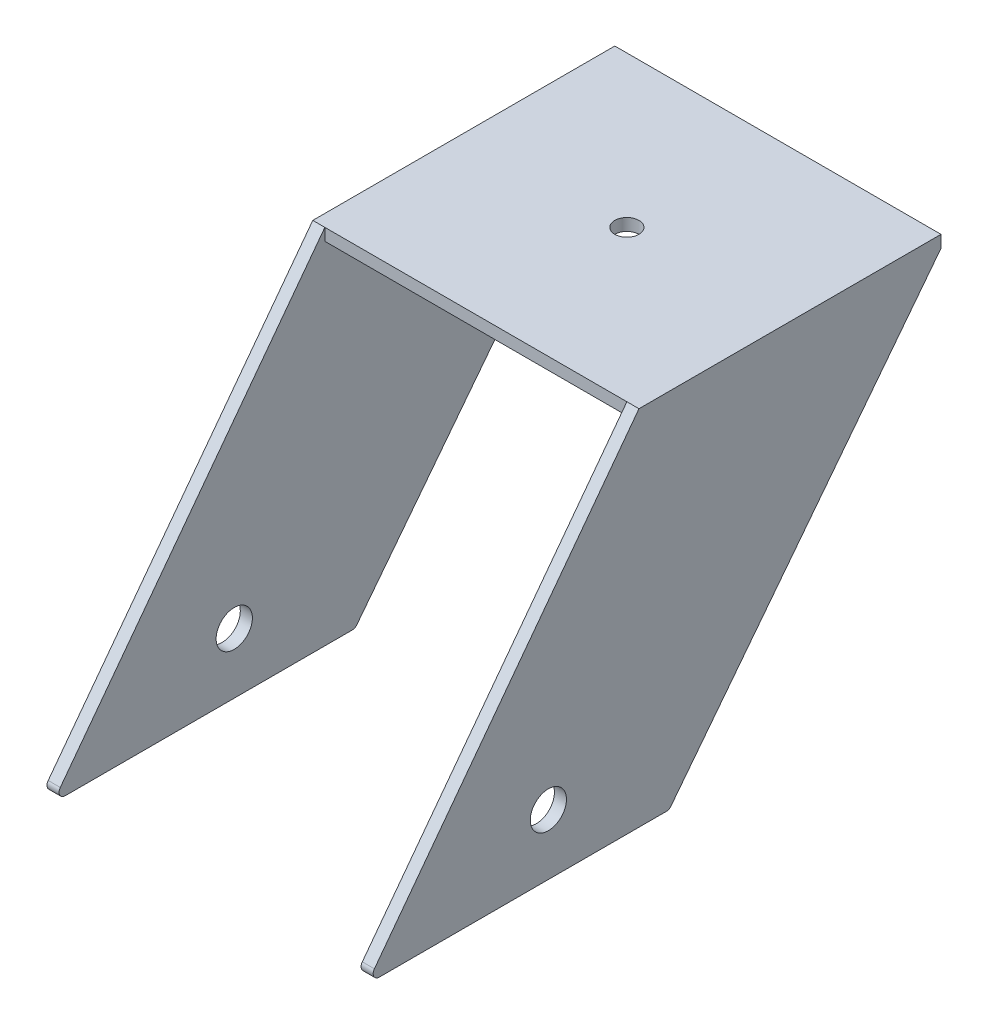
SolidWorks part; units mm, degrees
ref_plane "Front Plane" through (0, 0, 0) normal (0, 0, 1) x (1, 0, 0)
ref_plane "Top Plane" through (0, 0, 0) normal (0, 1, 0) x (1, 0, 0)
ref_plane "Right Plane" through (0, 0, 0) normal (1, 0, 0) x (0, 0, -1)
sketch "Sketch2" plane through (0, 0, 0) normal (0, 1, 0) x (1, 0, 0)
  line L1 (-25, 25) -> (25, 25)
  line L2 (-25, 25) -> (-25, -25)
  line L3 (-25, -25) -> (25, -25)
  line L4 (25, 25) -> (25, -25)
  circle A0 centre (0, 0) radius 2
  dimension "D5" = 4
  dimension "D1" = 50
  dimension "D2" = 50
  dimension "D3" = 25
  dimension "D4" = 25
extrude "Boss-Extrude1" add sketch "Sketch2" along normal blind 2
sketch "Sketch3" plane through (25, 0, 0) normal (1, 0, 0) x (0, 0, -1)
  line L0 (-25, 2) -> (-70, -58)
  line L1 (-70, -58) -> (-20, -58)
  line L2 (-20, -58) -> (25, 0)
  line L3 (-25, 2) -> (25, 2) construction
  line L4 (25, 0) -> (25, 2)
  line L5 (25, 2) -> (-25, 2)
  circle A0 centre (-40, -48) radius 3
  dimension "D6" = 6
  dimension "D1" = 50
  dimension "D2" = 40
  dimension "D3" = 50
  dimension "D5" = 10
  dimension "D4" = 30
sketch "Sketch4" plane through (-25, 0, 0) normal (-1, 0, 0) x (0, 0, 1)
  line L0 (25, 2) -> (-25, 2)
  line L1 (-25, 2) -> (-25, 0) construction
  line L2 (-25, 2) -> (25, 2) construction
  line L3 (-25, 0.0263) -> (-25, 2)
  line L6 (-25, 2.0263) -> (-25, -47.9737) construction
  line L8 (20, -58) -> (-25, 0.0263)
  line L9 (70, -58) -> (20, -58)
  line L10 (25, 2) -> (70, -58)
  circle A1 centre (40, -48) radius 3
  circle A2 centre (40, -48) radius 3 construction
  dimension "D1" = 6
extrude "Boss-Extrude2" add sketch "Sketch4" along normal blind 2
extrude "Boss-Extrude3" add sketch "Sketch3" along normal blind 2
fillet "Fillet1" radius 1 2 edges at (26, -58, 20) (-26, -58, 20)
fillet "Fillet2" radius 1 2 edges at (26, -58, 70) (-26, -58, 70)
equation "\"d\"= 40"
equation "\"D2@Sketch3\"=\"d\""
